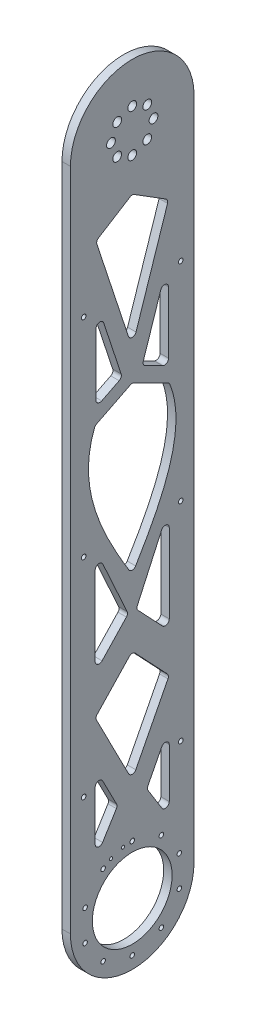
SolidWorks part; units mm, degrees
note: '?' marks a value the reader was unsure of.
material "6061 Alloy"
ref_plane "Front Plane" through (0, 0, 0) normal (0, 0, 1) x (1, 0, 0)
ref_plane "Top Plane" through (0, 0, 0) normal (0, 1, 0) x (1, 0, 0)
ref_plane "Right Plane" through (0, 0, 0) normal (1, 0, 0) x (0, 0, -1)
sketch "Sketch1" plane through (0, 0, 0) normal (1, 0, 0) x (0, -1, 0)
  line L0 (0, 0) -> (500, 0) construction
  line L1 (0, 46.5) -> (500, 46.5)
  line L2 (0, -46.5) -> (500, -46.5)
  arc A0 (0, 46.5) -> (0, -46.5) centre (0, 0) ccw
  arc A1 (500, -46.5) -> (500, 46.5) centre (500, 0) ccw
  circle A2 centre (0, 0) radius 16 construction
  circle A3 centre (-16, 0) radius 3.3
  circle A4 centre (-11.3137, 11.3137) radius 3.3
  circle A5 centre (0, 16) radius 3.3
  circle A6 centre (11.3137, 11.3137) radius 3.3
  circle A7 centre (16, 0) radius 3.3
  circle A8 centre (11.3137, -11.3137) radius 3.3
  circle A27 centre (500, 0) radius 37.25 construction
  circle A28 centre (537.25, 0) radius 1.7
  circle A29 centre (500, 0) radius 37.25 construction
  circle A30 centre (537.25, 0) radius 1.7
  circle A31 centre (530.1359, -21.895) radius 1.7
  circle A32 centre (511.5109, -35.4269) radius 1.7
  circle A33 centre (488.4891, -35.4269) radius 1.7
  circle A34 centre (469.8641, -21.895) radius 1.7
  circle A35 centre (462.75, 0) radius 1.7
  circle A36 centre (469.8641, 21.895) radius 1.7
  circle A37 centre (488.4891, 35.4269) radius 1.7
  circle A38 centre (511.5109, 35.4269) radius 1.7
  circle A39 centre (530.1359, 21.895) radius 1.7
  circle A40 centre (500, 0) radius 26
  circle A41 centre (0, -16) radius 3.3
  circle A42 centre (-11.3137, -11.3137) radius 3.3
  point P3 (250, 0)
  point P25 (0, 0)
  point P52 (500, 0)
  point P61 (500, 0)
  dimension "D3" = 32
  dimension "D4" = 6.6
  dimension "D2" = 74.5
  dimension "D7" = 3.4
  dimension "D8" = 3.4
  dimension "D10" = 52
  dimension "D6" = 46.5
  dimension "D1" = 500
  dimension "D5" = 8
  dimension "D9" = 10
extrude "Boss-Extrude1" add sketch "Sketch1" along normal blind 6.35 contours L2 A1 L1 A0 A40 A39 A38 A37 A36 A35 A34 A33 A32 A31 A28 A8 A7 A6 A5 A4 A3
ref_axis "Axis1" through (6.35, -500, 0) along (-1, 0, 0)?
sketch "Sketch3" plane through (6.35, 0, 0) normal (1, 0, 0) x (0, 0, -1)
  line L0 (0, -500) -> (0, 0) construction
  line L1 (0, -422.848) -> (27.8582, -368.6328)
  line L2 (0, -422.848) -> (-27.8582, -368.6328)
  line L3 (-27.8582, -368.6328) -> (0, -339.1393)
  line L4 (0, -339.1393) -> (27.8582, -368.6328)
  line L5 (0, -41.3687) -> (-27.3129, -58.4352)
  line L6 (-27.3129, -58.4352) -> (0, -141.249)
  line L7 (0, -141.249) -> (27.3129, -58.4352)
  line L8 (27.3129, -58.4352) -> (0, -41.3687)
  line L9 (3, -313.1891) -> (27.8582, -339.5065)
  line L10 (27.8582, -339.5065) -> (27.8582, -258.646)
  line L11 (27.8582, -258.646) -> (3, -313.1891)
  line L12 (-27.8582, -339.5065) -> (-27.8582, -258.646)
  line L13 (-3, -313.1891) -> (-27.8582, -339.5065)
  line L14 (-27.8582, -258.646) -> (-3, -313.1891)
  line L15 (-27.8582, -401.4529) -> (-11, -434.2608)
  line L16 (-11, -434.2608) -> (-27.8582, -461.4818)
  line L17 (-27.8582, -461.4818) -> (-27.8582, -401.4529)
  line L18 (11, -434.2608) -> (27.8582, -461.4818)
  line L19 (27.8582, -401.4529) -> (11, -434.2608)
  line L20 (27.8582, -461.4818) -> (27.8582, -401.4529)
  line L21 (0, -164.2489) -> (-27.8582, -178.2005)
  line L22 (0, -164.2489) -> (27.8582, -178.2005)
  line L23 (7.5, -156.821) -> (27.3129, -96.7475)
  line L24 (27.3129, -96.7475) -> (27.3129, -166.7434)
  line L25 (27.3129, -166.7434) -> (7.5, -156.821)
  line L26 (-27.3129, -96.7475) -> (-27.3129, -166.7434)
  line L27 (-7.5, -156.821) -> (-27.3129, -96.7475)
  line L28 (-27.3129, -166.7434) -> (-7.5, -156.821)
  spline S0 degree 3 poles (-27.8582, -178.2005) (-43.7791, -216.0933) (-18.6166, -258.2761) (0, -289.085) knots 0 0 0 0 1 1 1 1
  spline S1 degree 3 poles (27.8582, -178.2005) (43.7791, -216.0933) (18.6166, -258.2761) (0, -289.085) knots 0 0 0 0 1 1 1 1
  dimension "D1" = 15
  dimension "D2" = 20
  dimension "D3" = 12
  dimension "D4" = 10
  dimension "D5" = 6
  dimension "D6" = 15
  dimension "D7" = 22
extrude "Cut-Extrude1" cut sketch "Sketch3" against normal through all
fillet "Fillet1" radius 3 30 edges at (3.175, -58.4352, -27.3129) (3.175, -41.3687, 0) (3.175, -58.4352, 27.3129) (3.175, -141.249, 0) (3.175, -289.085, 0) (3.175, -164.2489, 0) (3.175, -401.4529, 27.8582) (3.175, -434.2608, 11) (3.175, -461.4818, 27.8582) (3.175, -461.4818, -27.8582) (3.175, -434.2608, -11) (3.175, -401.4529, -27.8582) (3.175, -368.6328, -27.8582) (3.175, -339.1393, 0) (3.175, -368.6328, 27.8582) (3.175, -422.848, 0) (3.175, -313.1891, 3) (3.175, -339.5065, 27.8582) (3.175, -258.646, 27.8582) (3.175, -178.2005, -27.8582) (3.175, -178.2005, 27.8582) (3.175, -339.5065, -27.8582) (3.175, -313.1891, -3) (3.175, -258.646, -27.8582) (3.175, -96.7475, 27.3129) (3.175, -166.7434, 27.3129) (3.175, -156.821, 7.5) (3.175, -166.7434, -27.3129) (3.175, -156.821, -7.5) (3.175, -96.7475, -27.3129)
sketch "Sketch4" plane through (6.35, 0, 0) normal (1, 0, 0) x (0, 0, -1)
  line L0 (0, 46.5) -> (-113.1579, 46.5) construction
  line L1 (-46.5, 0) -> (-46.5, -500) construction
  line L2 (-46.5, -100) -> (46.5, -100) construction
  line L3 (46.5, 0) -> (46.5, -500) construction
  line L4 (-46.5, -106.35) -> (46.5, -106.35) construction
  line L5 (-36.5, -100) -> (-36.5, -106.35) construction
  line L6 (0, 0) -> (0, -106.35) construction
  line L7 (0, -106.35) -> (0, -256.35) construction
  line L8 (0, -256.35) -> (46.5, -256.35) construction
  line L9 (46.5, -262.7) -> (-46.5, -262.7) construction
  line L10 (0, -181.35) -> (46.5, -181.35) construction
  line L11 (0, -262.7) -> (0, -412.7) construction
  line L12 (0, -412.7) -> (46.5, -412.7) construction
  line L13 (0, -337.7) -> (46.5, -337.7) construction
  arc A1 (46.5, 0) -> (-46.5, 0) centre (0, 0) ccw construction
  circle A2 centre (-36.5, -103.175) radius 1.75
  circle A3 centre (36.5, -103.175) radius 1.75
  circle A4 centre (-36.5, -259.525) radius 1.75
  circle A5 centre (36.5, -259.525) radius 1.75
  circle A6 centre (-36.5, -415.875) radius 1.75
  circle A7 centre (36.5, -415.875) radius 1.75
  point P17 (-36.5, -103.175)
  dimension "D1" = 3.5
  dimension "D2" = 6.35
  dimension "D3" = 10
  dimension "D4" = 146.5
  dimension "D5" = 150
  dimension "D6" = 6.35
  dimension "D7" = 81.35
  dimension "D8" = 150
  dimension "D9" = 81.35
extrude "Cut-Extrude2" cut sketch "Sketch4" against normal through all
sketch "Sketch5" plane through (6.35, 0, 0) normal (1, 0, 0) x (0, 0, -1)
  line L0 (-6.9161, -463.3431) -> (-15.9511, -466.2787) construction
  line L1 (-7.2252, -475.0096) -> (7.4545, -470.2399) construction
  line L2 (-21.895, -469.8641) -> (0, -462.75) construction
  line L3 (-10.9475, -466.3071) -> (0, -500) construction
  circle A0 centre (-6.9161, -463.3431) radius 1.2
  circle A1 centre (-15.9511, -466.2787) radius 1.2
  circle A2 centre (0, -500) radius 26 construction
  circle A3 centre (0, -500) radius 26 construction
  circle A4 centre (0, -462.75) radius 1.7 construction
  circle A5 centre (-21.895, -469.8641) radius 1.7 construction
  circle A6 centre (0, -462.75) radius 1.7 construction
  circle A7 centre (-21.895, -469.8641) radius 1.7 construction
  point P16 (-11.4336, -464.8109)
  dimension "D1" = 2.4
  dimension "D2" = 9.5
  dimension "D3" = 11
extrude "Cut-Extrude4" cut sketch "Sketch5" against normal through all
sketch "Sketch6" plane through (6.35, 0, 0) normal (1, 0, 0) x (0, 0, -1)
  line L2 (-23.6842, -540.0163) -> (-29.9682, -544.1104) construction
  line L3 (-44.1104, -529.9682) -> (-29.9682, -544.1104)
  line L4 (0, -500) -> (0, -546.5) construction
  line L5 (-37.0393, -537.0393) -> (0, -500) construction
  line L6 (-44.1104, -529.9682) -> (-40.0163, -523.6842) construction
  arc A0 (-46.5, -500) -> (46.5, -500) centre (0, -500) ccw construction
  arc A1 (-29.9682, -544.1104) -> (-16.4747, -543.4837) centre (-22.4977, -559.381) cw
  arc A4 (-44.1104, -529.9682) -> (-43.4837, -516.4747) centre (-59.381, -522.4977) ccw
  arc A5 (-16.4747, -543.4837) -> (-43.4837, -516.4747) centre (0, -500) cw
  dimension "D2" = 17
  dimension "D4" = 17
  dimension "D1" = 20
  dimension "D3" = 8
  dimension "D5" = 8
  dimension "D6" = 7.5
  dimension "D7" = 45
  dimension "D8" = 7.5
extrude "Boss-Extrude2" add sketch "Sketch6" against normal up to surface (6.35 mm away) up to face at (0, -463.3431, 5.7161)
sketch "Sketch7" plane through (0, -287.0393, 287.0393) normal (0, -0.7071, 0.7071) x (1, 0, 0)
  line L0 (0, -343.5534) -> (6.35, -343.5534) construction
  line L1 (0, -363.5534) -> (6.35, -363.5534) construction
  line L2 (0, -363.5534) -> (0, -343.5534) construction
  point P0 (3.175, -347.5534)
  point P1 (3.175, -360.5841)
  dimension "D1" = 4
  dimension "D2" = 2.9693
  dimension "D3" = 3.175
hole_wizard "Tap Drill for M3x0.5 Tap1" positions "Sketch7" profile "Sketch8" hole size "M3x0.5" standard "ANSI Metric"
sketch "Sketch8" plane through (3.175, -532.7967, 41.282) normal (1, 0, 0) x (0, -0.7071, -0.7071)
  line L0 (0, 0) -> (0, 5.7511)
  line L1 (0, 5.7511) -> (1.25, 5)
  line L2 (1.25, 5) -> (1.25, 0)
  line L5 (1.25, 0) -> (0, 0)
  line L10 (0, 5.7511) -> (-1.25, 5) construction
  line L11 (0, -6.35) -> (0, 107.95) construction
  dimension "Hole Dia." = 2.5
  dimension "Hole Depth" = 5
  dimension "Drill Angle" = 118
pattern_circular "CirPattern1" count 2 every 90 about axis through (0, -500, 0) along (1, 0, 0) of "Boss-Extrude2", "Tap Drill for M3x0.5 Tap1"
sketch "Sketch9" plane through (6.35, 0, 0) normal (1, 0, 0) x (0, 0, -1)
  line L0 (-43.4837, -516.4747) -> (-63.4837, -516.4747)
  line L1 (43.4837, -516.4747) -> (63.4837, -516.4747)
  arc A0 (43.4837, -516.4747) -> (-43.4837, -516.4747) centre (0, -500) cw
  arc A1 (43.4837, -516.4747) -> (46.5, -500) centre (0, -500) ccw construction
  arc A2 (-63.4837, -516.4747) -> (63.4837, -516.4747) centre (0, -500) ccw
  dimension "D1" = 20
extrude "Cut-Extrude5" cut sketch "Sketch9" against normal through all
sketch "Sketch10" plane through (6.35, 0, 0) normal (1, 0, 0) x (0, 0, -1)
  circle A0 centre (0, -500) radius 30
  circle A1 centre (0, -500) radius 26 construction
  dimension "D1" = 60
extrude "Cut-Extrude6" cut sketch "Sketch10" against normal through all
equation "\"L1L\"=500"
equation "\"D1@Sketch1\"=\"L1L\""
equation "\"L1Thick\"=6.35"
equation "\"D1@Boss-Extrude1\"=\"L1Thick\""
equation "\"Harm-Drive-Outer\"=74.5"
equation "\"D2@Sketch1\"=\"Harm-Drive-Outer\""
